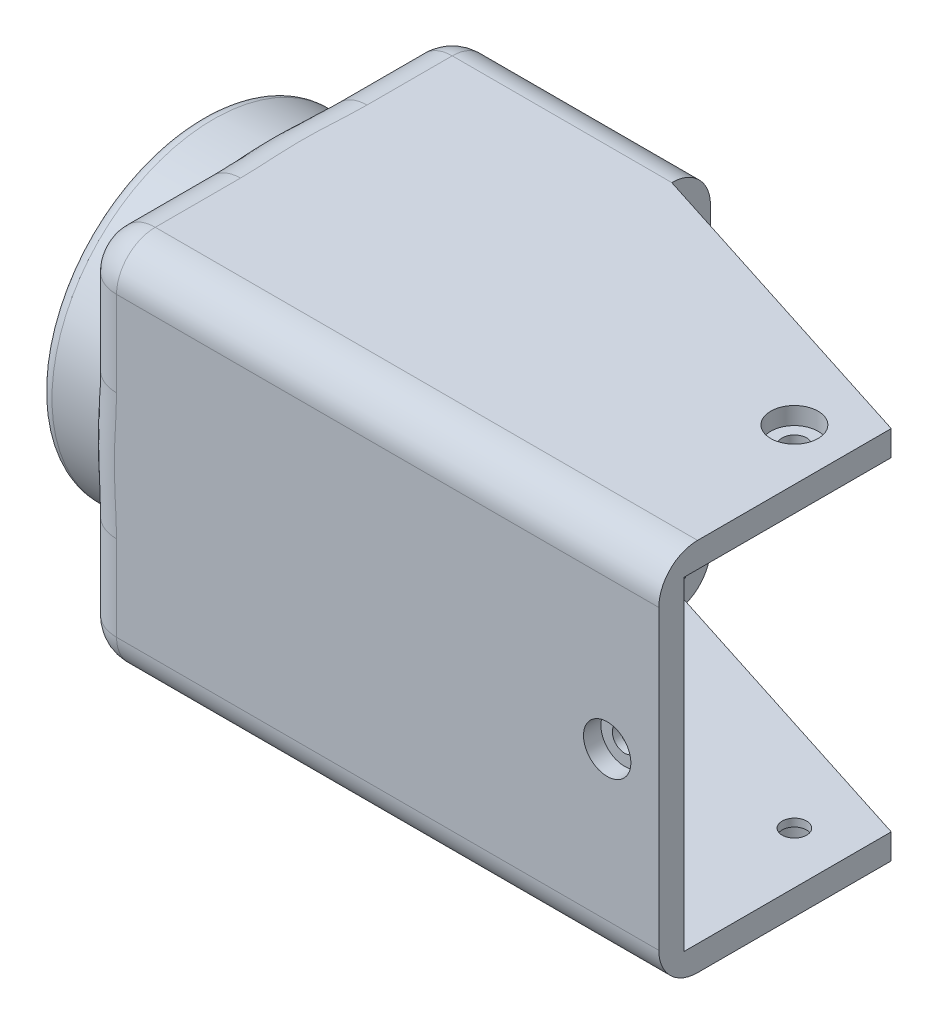
SolidWorks part; units mm, degrees
note: The reader was unsure of these and kept them because the rebuilt part matched: shared geometry of "草图1<3>", "草图1<4>", "草图1<5>", "草图1<6>".
ref_plane "前视基准面" through (0, 0, 0) normal (0, 0, 1) x (1, 0, 0)
ref_plane "上视基准面" through (0, 0, 0) normal (0, 1, 0) x (1, 0, 0)
ref_plane "右视基准面" through (0, 0, 0) normal (1, 0, 0) x (0, 0, -1)
other "Configuration Table"
sketch "草图1" plane through (0, 0, 0) normal (1, 0, 0) x (0, 0, -1)
  line L1 (-20.488, -14.9861) -> (8.512, -14.9861)
  line L2 (-20.488, -14.9861) -> (-20.488, 14.0139)
  line L3 (-20.488, 14.0139) -> (8.512, 14.0139)
  line L4 (8.512, -14.9861) -> (8.512, 14.0139)
  line L5 (-20.488, -14.9861) -> (8.512, 14.0139) construction
  line L6 (-20.488, 14.0139) -> (8.512, -14.9861) construction
  circle A0 centre (-5.988, -0.4861) radius 12.5
  circle A1 centre (-5.988, -0.4861) radius 4
  circle A2 centre (-5.988, 7.5139) radius 2.5
  circle A3 centre (-5.988, 7.5139) radius 3.1
  circle A10 centre (2.012, -0.4861) radius 2.5
  circle A11 centre (2.012, -0.4861) radius 3.1
  circle A12 centre (-5.988, -8.4861) radius 2.5
  circle A13 centre (-5.988, -8.4861) radius 3.1
  circle A14 centre (-13.988, -0.4861) radius 2.5
  circle A15 centre (-13.988, -0.4861) radius 3.1
  point P24 (-3.237, 2.7509)
  point P25 (-5.988, -0.4861)
  dimension "D1" = 25
  dimension "D2" = 8
  dimension "D3" = 5
  dimension "D4" = 6.2
  dimension "D5" = 8
  dimension "D6" = 29
  dimension "D7" = 4
extrude "凸台-拉伸1" add sketch "草图1" along normal blind 7.8 contours A0
extrude "凸台-拉伸2" add sketch "草图1<3>" along normal blind 45 from offset 5 contours L3 L4 L1 L2 | A0
sketch "草图1<3>" plane through (0, 0, 0) normal (1, 0, 0) x (0, 0, -1) same geometry as "草图1"
extrude "切除-拉伸1" cut sketch "草图1<4>" along normal up to next contours A2 | A10 | A12 | A14 | A1
sketch "草图1<4>" plane through (0, 0, 0) normal (1, 0, 0) x (0, 0, -1) same geometry as "草图1"
extrude "切除-拉伸2" cut sketch "草图1<5>" along normal blind 1.5 contours A11 A10 | A3 A2 | A15 A14 | A13 A12
sketch "草图1<5>" plane through (0, 0, 0) normal (1, 0, 0) x (0, 0, -1) same geometry as "草图1"
extrude "切除-拉伸3" cut sketch "草图1<6>" against normal blind 1.5 from surface at 7.8 contours A3 A2 | A15 A14 | A11 A10 | A13 A12 starting at face at (7.8, 7.5139, 3.488)
sketch "草图1<6>" plane through (0, 0, 0) normal (1, 0, 0) x (0, 0, -1) same geometry as "草图1"
sketch "草图2" plane through (50, 0, 0) normal (1, 0, 0) x (0, 0, -1)
  line L1 (-18.538, 12.0639) -> (6.562, 12.0639)
  line L2 (-18.538, 12.0639) -> (-18.538, -13.0361)
  line L3 (-18.538, -13.0361) -> (6.562, -13.0361)
  line L4 (6.562, 12.0639) -> (6.562, -13.0361)
  line L5 (-18.538, 12.0639) -> (6.562, -13.0361) construction
  line L6 (-18.538, -13.0361) -> (6.562, 12.0639) construction
  point P0 (-5.988, -0.4861)
  dimension "D1" = 25.1
extrude "切除-拉伸4" cut sketch "草图2" against normal blind 40
fillet "圆角1" radius 3 4 edges at (27.5, 14.0139, 20.488) (27.5, -14.9861, 20.488) (27.5, 14.0139, -8.512) (27.5, -14.9861, -8.512)
fillet "圆角2" radius 3 8 edges at (5, -14.1074, -7.6333) (5, -14.9861, 5.988) (5, -14.1074, 19.6093) (5, -0.4861, 20.488) (5, 13.1352, 19.6093) (5, 14.0139, 5.988) (5, 13.1352, -7.6333) (5, -0.4861, -8.512)
fillet "圆角4" radius 1 1 edges at (0, -0.4861, -6.512)
hole_wizard "孔1" positions "草图3" profile "草图4" legacy
sketch "草图3" plane through (0, 0, -8.512) normal (0, 0, -1) x (-1, 0, 0)
  line L0 (-50, -11.9861) -> (-50, 11.0139) construction
  line L1 (-46, 11.0139) -> (-46, -11.9861)
  line L2 (-8, 11.0139) -> (-50, 11.0139) construction
  line L3 (-50, -11.9861) -> (-8, -11.9861) construction
  point P0 (-46, -0.4861)
  dimension "D1" = 4
sketch "草图4" plane through (46, -0.4861, -8.512) normal (1, 0, 0) x (0, 1, 0)
  line L0 (0, 0) -> (0, 4)
  line L1 (0, 4) -> (0.95, 4)
  line L2 (0.95, 4) -> (0.95, 1.35)
  line L3 (0.95, 1.35) -> (1.835, 1.35)
  line L4 (1.835, 1.35) -> (1.835, 0)
  line L5 (1.835, 0) -> (0, 0)
  line L6 (0, 110) -> (0, -10) construction
  dimension "直径" = 1.9
  dimension "深度" = 4
  dimension "柱坑直径" = 3.67
  dimension "柱坑深度" = 1.35
hole_wizard "孔2" positions "草图5" profile "草图6" legacy
sketch "草图5" plane through (0, -14.9861, 0) normal (0, -1, 0) x (-1, 0, 0)
  line L0 (-50, -17.488) -> (-50, 5.512) construction
  line L1 (-46, 5.512) -> (-46, -17.488)
  line L2 (-8, 5.512) -> (-50, 5.512) construction
  line L3 (-50, -17.488) -> (-8, -17.488) construction
  point P0 (-46, -5.988)
  dimension "D1" = 4
sketch "草图6" plane through (46, -14.9861, 5.988) normal (1, 0, 0) x (0, 0, -1)
  line L0 (0, 0) -> (0, 4)
  line L1 (0, 4) -> (0.95, 4)
  line L2 (0.95, 4) -> (0.95, 1.35)
  line L3 (0.95, 1.35) -> (1.835, 1.35)
  line L4 (1.835, 1.35) -> (1.835, 0)
  line L5 (1.835, 0) -> (0, 0)
  line L6 (0, 110) -> (0, -10) construction
  dimension "直径" = 1.9
  dimension "深度" = 4
  dimension "柱坑直径" = 3.67
  dimension "柱坑深度" = 1.35
hole_wizard "孔3" positions "草图7" profile "草图8" legacy
sketch "草图7" plane through (0, 0, 20.488) normal (0, 0, 1) x (1, 0, 0)
  line L0 (50, -11.9861) -> (50, 11.0139) construction
  line L1 (46, 11.0139) -> (46, -11.9861)
  line L2 (50, 11.0139) -> (8, 11.0139) construction
  line L3 (8, -11.9861) -> (50, -11.9861) construction
  point P0 (46, -0.4861)
  dimension "D1" = 4
sketch "草图8" plane through (46, -0.4861, 20.488) normal (1, 0, 0) x (0, -1, 0)
  line L0 (0, 0) -> (0, 4)
  line L1 (0, 4) -> (0.95, 4)
  line L2 (0.95, 4) -> (0.95, 1.35)
  line L3 (0.95, 1.35) -> (1.835, 1.35)
  line L4 (1.835, 1.35) -> (1.835, 0)
  line L5 (1.835, 0) -> (0, 0)
  line L6 (0, 110) -> (0, -10) construction
  dimension "直径" = 1.9
  dimension "深度" = 4
  dimension "柱坑直径" = 3.67
  dimension "柱坑深度" = 1.35
hole_wizard "孔4" positions "草图9" profile "草图10" legacy
sketch "草图9" plane through (0, 14.0139, 0) normal (0, 1, 0) x (1, 0, 0)
  line L0 (50, -17.488) -> (50, 5.512) construction
  line L1 (46, 5.512) -> (46, -17.488)
  line L2 (50, 5.512) -> (8, 5.512) construction
  line L3 (8, -17.488) -> (50, -17.488) construction
  point P0 (46, -5.988)
  dimension "D1" = 4
sketch "草图10" plane through (46, 14.0139, 5.988) normal (1, 0, 0) x (0, 0, 1)
  line L0 (0, 0) -> (0, 4)
  line L1 (0, 4) -> (0.95, 4)
  line L2 (0.95, 4) -> (0.95, 1.35)
  line L3 (0.95, 1.35) -> (1.835, 1.35)
  line L4 (1.835, 1.35) -> (1.835, 0)
  line L5 (1.835, 0) -> (0, 0)
  line L6 (0, 110) -> (0, -10) construction
  dimension "直径" = 1.9
  dimension "深度" = 4
  dimension "柱坑直径" = 3.67
  dimension "柱坑深度" = 1.35
sketch "草图11" plane through (0, 0, -8.512) normal (0, 0, -1) x (-1, 0, 0)
  line L0 (-8, -14.9861) -> (-50, -14.9861) construction
  line L1 (-50, 14.0139) -> (-25, 14.0139)
  line L2 (-50, 14.0139) -> (-50, -14.9861)
  line L3 (-50, -14.9861) -> (-25, -14.9861)
  line L4 (-25, 14.0139) -> (-25, -14.9861)
  dimension "D1" = 25
extrude "切除-拉伸5" cut sketch "草图11" against normal blind 3
sketch "草图12" plane through (0, -14.9861, 0) normal (0, -1, 0) x (1, 0, 0)
  line L0 (50, -5.512) -> (50, 2.488)
  line L1 (50, 17.488) -> (50, -5.512) construction
  line L2 (50, 2.488) -> (25, -5.512)
  line L3 (25, -5.512) -> (50, -5.512)
  dimension "D1" = 8
extrude "切除-拉伸6" cut sketch "草图12" against normal through all
